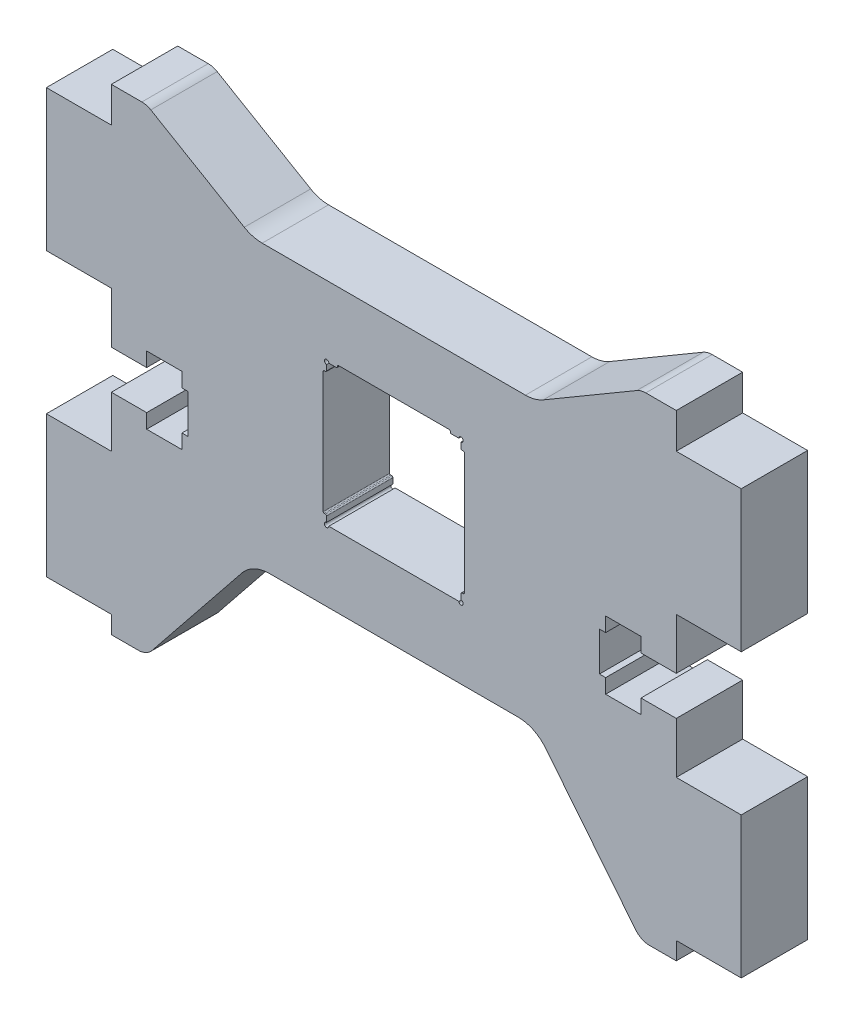
SolidWorks part; units mm, degrees
ref_plane "Front Plane" through (0, 0, 0) normal (0, 0, 1) x (1, 0, 0)
ref_plane "Top Plane" through (0, 0, 0) normal (0, 1, 0) x (1, 0, 0)
ref_plane "Right Plane" through (0, 0, 0) normal (1, 0, 0) x (0, 0, -1)
sketch "Sketch1" plane through (0, 0, 0) normal (0, 0, 1) x (1, 0, 0)
  line L0 (0, 0) -> (0, -22.987) construction
  line L1 (6.0452, -6.35) -> (-6.0452, -6.35)
  line L2 (6.0452, -6.35) -> (6.0452, 6.35)
  line L3 (6.0452, 6.35) -> (-6.0452, 6.35)
  line L4 (-6.0452, -6.35) -> (-6.0452, 6.35)
  line L5 (6.0452, -6.35) -> (-6.0452, 6.35) construction
  line L6 (6.0452, 6.35) -> (-6.0452, -6.35) construction
  line L7 (25.4, -22.987) -> (-25.4, -22.987) construction
  line L8 (25.4, 2.413) -> (25.4, -10.287)
  line L9 (25.4, -22.987) -> (31.242, -22.987)
  line L10 (-31.242, 2.413) -> (-25.4, 2.413)
  line L11 (31.242, -10.287) -> (25.4, -10.287)
  line L12 (31.242, -22.987) -> (31.242, -10.287)
  line L13 (25.4, -22.987) -> (25.4, -24.5745)
  line L14 (-12.7, -12.7) -> (12.7, -12.7)
  line L15 (12.7, -12.7) -> (22.225, -24.5745)
  line L16 (22.225, -24.5745) -> (25.4, -24.5745)
  line L17 (-12.7, 12.7) -> (12.7, 12.7)
  line L18 (-12.7, 12.7) -> (-22.225, 18.288)
  line L19 (-31.242, -10.287) -> (-25.4, -10.287)
  line L20 (-31.242, -22.987) -> (-31.242, -10.287)
  line L21 (-25.4, -22.987) -> (-31.242, -22.987)
  line L22 (-25.4, -22.987) -> (-25.4, -24.5745)
  line L23 (-22.225, -24.5745) -> (-25.4, -24.5745)
  line L24 (-12.7, -12.7) -> (-22.225, -24.5745)
  line L25 (-25.4, 18.288) -> (-22.225, 18.288)
  line L26 (-25.4, 2.413) -> (-25.4, -10.287)
  line L27 (31.242, 2.413) -> (25.4, 2.413)
  line L28 (31.242, 2.413) -> (31.242, 15.113)
  line L29 (31.242, 15.113) -> (25.4, 15.113)
  line L30 (25.4, 15.113) -> (25.4, 18.288)
  line L31 (25.4, 18.288) -> (22.225, 18.288)
  line L32 (-25.4, 15.113) -> (-25.4, 18.288)
  line L33 (12.7, 12.7) -> (22.225, 18.288)
  line L34 (-31.242, 15.113) -> (-25.4, 15.113)
  line L35 (-31.242, 2.413) -> (-31.242, 15.113)
  point P0 (0, 0)
  point P11 (0, -22.987)
  point P28 (0, -12.7)
  point P29 (0, 12.7)
  dimension "D1" = 12.7
  dimension "D2" = 12.0904
  dimension "D3" = 16.637
  dimension "D4" = 50.8
  dimension "D5" = 12.7
  dimension "D6" = 5.842
  dimension "D7" = 12.7
  dimension "D8" = 1.5875
  dimension "D9" = 12.7
  dimension "D10" = 6.35
  dimension "D11" = 3.175
  dimension "D12" = 6.35
  dimension "D13" = 12.7
  dimension "D16" = 12.7
  dimension "D17" = 3.175
  dimension "D18" = 3.175
extrude "Boss-Extrude1" add sketch "Sketch1" along normal blind 5.969
sketch "Sketch2" plane through (0, 0, 5.969) normal (0, 0, 1) x (1, 0, 0)
  line L0 (-25.4, -3.937) -> (25.4, -3.937) construction
  line L1 (-25.4, 2.413) -> (-25.4, -10.287) construction
  line L2 (25.4, -10.287) -> (25.4, 2.413) construction
  line L3 (22.225, -2.1844) -> (22.225, -0.889)
  line L4 (22.225, -5.6896) -> (25.4, -5.6896)
  line L5 (0, -3.937) -> (0, -12.7) construction
  line L6 (22.225, -2.1844) -> (25.4, -2.1844)
  line L7 (25.4, -5.6896) -> (25.4, -2.1844)
  line L8 (22.225, -5.6896) -> (25.4, -2.1844) construction
  line L9 (22.225, -2.1844) -> (25.4, -5.6896) construction
  line L10 (19.05, -6.985) -> (22.225, -6.985)
  line L11 (19.05, -6.985) -> (19.05, -5.6896)
  line L12 (19.05, -0.889) -> (22.225, -0.889)
  line L13 (22.225, -6.985) -> (22.225, -5.6896)
  line L14 (19.05, -6.985) -> (22.225, -0.889) construction
  line L15 (19.05, -0.889) -> (22.225, -6.985) construction
  line L16 (18.492, -5.6896) -> (19.05, -5.6896)
  line L17 (18.492, -5.6896) -> (18.492, -2.1844)
  line L18 (18.492, -2.1844) -> (19.05, -2.1844)
  line L19 (-12.7, -12.7) -> (12.7, -12.7) construction
  line L20 (18.492, -5.6896) -> (19.05, -2.1844) construction
  line L21 (18.492, -2.1844) -> (19.05, -5.6896) construction
  line L22 (19.05, -2.1844) -> (19.05, -0.889)
  line L23 (-18.492, -2.1844) -> (-19.05, -5.6896) construction
  line L24 (-18.492, -5.6896) -> (-19.05, -2.1844) construction
  line L25 (-19.05, -0.889) -> (-22.225, -6.985) construction
  line L26 (-19.05, -6.985) -> (-22.225, -0.889) construction
  line L27 (-22.225, -2.1844) -> (-25.4, -5.6896) construction
  line L28 (-22.225, -5.6896) -> (-25.4, -2.1844) construction
  line L29 (-19.05, -2.1844) -> (-19.05, -0.889)
  line L30 (-18.492, -2.1844) -> (-19.05, -2.1844)
  line L31 (-18.492, -5.6896) -> (-18.492, -2.1844)
  line L32 (-18.492, -5.6896) -> (-19.05, -5.6896)
  line L33 (-22.225, -6.985) -> (-22.225, -5.6896)
  line L34 (-19.05, -0.889) -> (-22.225, -0.889)
  line L35 (-19.05, -6.985) -> (-19.05, -5.6896)
  line L36 (-19.05, -6.985) -> (-22.225, -6.985)
  line L37 (-25.4, -5.6896) -> (-25.4, -2.1844)
  line L38 (-22.225, -2.1844) -> (-25.4, -2.1844)
  line L39 (-22.225, -5.6896) -> (-25.4, -5.6896)
  line L40 (-22.225, -2.1844) -> (-22.225, -0.889)
  point P6 (23.8125, -3.937)
  point P11 (20.6375, -3.937)
  point P16 (18.771, -3.937)
  point P37 (-18.771, -3.937)
  point P38 (-20.6375, -3.937)
  point P39 (-23.8125, -3.937)
  dimension "D1" = 3.175
  dimension "D2" = 3.175
  dimension "D3" = 3.5052
  dimension "D4" = 6.096
  dimension "D5" = 0.558
extrude "Cut-Extrude1" cut sketch "Sketch2" against normal through all
sketch "Sketch3" plane through (0, 0, 5.969) normal (0, 0, 1) x (1, 0, 0)
  line L0 (-6.0452, 0) -> (6.0452, 0) construction
  line L1 (-6.0452, 6.35) -> (-6.0452, -6.35) construction
  line L2 (6.0452, -6.35) -> (6.0452, 6.35) construction
  circle A0 centre (6.0452, 6.35) radius 0.1984
  circle A1 centre (-6.0452, 6.35) radius 0.1984
  circle A2 centre (-6.0452, -6.35) radius 0.1984
  circle A3 centre (6.0452, -6.35) radius 0.1984
  dimension "D1" = 0.3969
  dimension "D2" = 0.3969
extrude "Cut-Extrude2" cut sketch "Sketch3" against normal through all
fillet "Fillet1" radius 3.175 4 edges at (-12.7, -12.7, 2.9845) (12.7, -12.7, 2.9845) (12.7, 12.7, 2.9845) (-12.7, 12.7, 2.9845)
fillet "Fillet2" radius 1.5875 4 edges at (22.225, -24.5745, 2.9845) (-22.225, -24.5745, 2.9845) (-22.225, 18.288, 2.9845) (22.225, 18.288, 2.9845)
sketch "Sketch4" plane through (0, 0, 5.969) normal (0, 0, 1) x (1, 0, 0)
  line L0 (-6.0452, 0) -> (6.0452, 0) construction
  line L1 (-6.0452, 6.1516) -> (-6.0452, -6.1516) construction
  line L2 (6.0452, -6.1516) -> (6.0452, 6.1516) construction
  line L4 (6.35, -5.5562) -> (-6.35, -5.5563)
  line L5 (6.35, -5.5562) -> (6.35, 5.5563)
  line L6 (6.35, 5.5563) -> (-6.35, 5.5562)
  line L7 (-6.35, -5.5563) -> (-6.35, 5.5562)
  line L8 (6.35, -5.5562) -> (-6.35, 5.5562) construction
  line L9 (6.35, 5.5563) -> (-6.35, -5.5563) construction
  point P6 (0, 0)
  dimension "D1" = 12.7
  dimension "D2" = 11.1125
extrude "Cut-Extrude3" cut sketch "Sketch4" against normal through all
fillet "Fillet7" radius 0.1 8 edges at (6.35, -5.5562, 2.9845) (6.0452, -5.5562, 2.9845) (6.35, 5.5563, 2.9845) (6.0452, 5.5563, 2.9845) (-6.0452, 5.5562, 2.9845) (-6.35, 5.5562, 2.9845) (-6.35, -5.5563, 2.9845) (-6.0452, -5.5563, 2.9845)
sketch "Sketch5" plane through (0, 0, 5.969) normal (0, 0, 1) x (1, 0, 0)
  line L0 (5.8468, 6.35) -> (-5.8468, 6.35) construction
  line L1 (5.08, 6.1) -> (-5.08, 6.1)
  line L2 (5.08, 6.1) -> (5.08, 6.6)
  line L3 (5.08, 6.6) -> (-5.08, 6.6)
  line L4 (-5.08, 6.1) -> (-5.08, 6.6)
  line L5 (5.08, 6.1) -> (-5.08, 6.6) construction
  line L6 (5.08, 6.6) -> (-5.08, 6.1) construction
  point P0 (0, 6.35)
  dimension "D1" = 10.16
  dimension "D2" = 0.5
extrude "Cut-Extrude4" cut sketch "Sketch5" against normal through all
fillet "Fillet8" radius 0.1 4 edges at (5.08, 6.6, 2.9845) (5.08, 6.35, 2.9845) (-5.08, 6.6, 2.9845) (-5.08, 6.35, 2.9845)
sketch "Sketch6" [suppressed] plane through (0, 0, 5.969) normal (0, 0, 1) x (1, 0, 0)
  line L0 (-12.7, 12.7) -> (-12.7, -12.7) construction
  line L1 (11.8374, 12.7) -> (-11.8374, 12.7) construction
  line L2 (-11.1766, -12.7) -> (11.1766, -12.7) construction
  line L3 (-15.7, 6.35) -> (-9.7, 6.35) construction
  line L4 (-15.7, 7.35) -> (-9.7, 7.35)
  line L5 (-15.7, 5.35) -> (-9.7, 5.35)
  line L6 (-15.7, 0) -> (-9.7, 0) construction
  line L7 (-15.7, 1) -> (-9.7, 1)
  line L8 (-15.7, -1) -> (-9.7, -1)
  arc A0 (-15.7, 7.35) -> (-15.7, 5.35) centre (-15.7, 6.35) ccw
  arc A1 (-9.7, 5.35) -> (-9.7, 7.35) centre (-9.7, 6.35) ccw
  arc A2 (-15.7, 1) -> (-15.7, -1) centre (-15.7, 0) ccw
  arc A3 (-9.7, -1) -> (-9.7, 1) centre (-9.7, 0) ccw
  point P8 (-12.7, 6.35)
  point P17 (-12.7, 0)
  point P18 (-12.7, -2.413)
  dimension "D2" = 1
  dimension "D1" = 6
  dimension "D3" = 12.7
  dimension "D5" = 6.35
extrude "Cut-Extrude5" [suppressed] cut sketch "Sketch6" against normal through all
